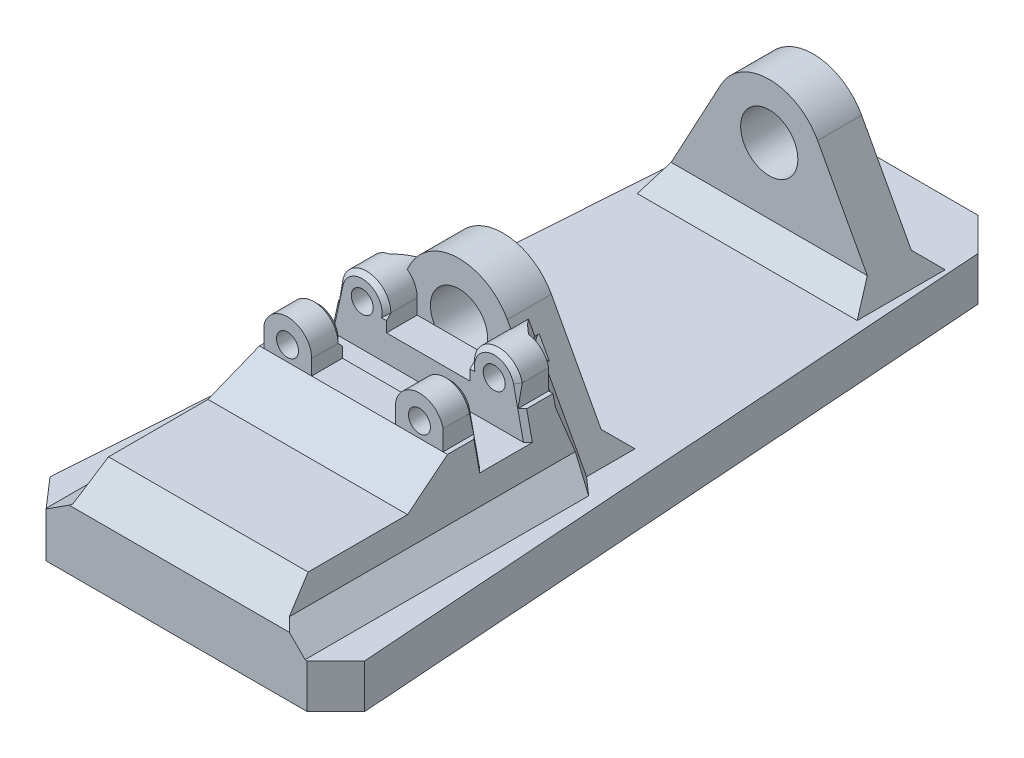
SolidWorks part; units mm, degrees
material "ABS"
ref_plane "Front Plane" through (0, 0, 0) normal (0, 0, 1) x (1, 0, 0)
ref_plane "Top Plane" through (0, 0, 0) normal (0, 1, 0) x (1, 0, 0)
ref_plane "Right Plane" through (0, 0, 0) normal (1, 0, 0) x (0, 0, -1)
sketch "Sketch1" plane through (0, 0, 0) normal (0, 0, 1) x (1, 0, 0)
  line L0 (0, -883.4014) -> (0, -903.4014) construction
  line L1 (-25, -903.4014) -> (25, -903.4014)
  line L2 (-10.9999, -877.464) -> (-25, -903.4014)
  line L3 (25, -903.4014) -> (10.9999, -877.464)
  circle A0 centre (0, -883.4014) radius 6.5
  circle A1 centre (0, -883.4014) radius 12.5
  point P9 (0, -903.4014)
  dimension "D1" = 13
  dimension "D2" = 25
  dimension "D3" = 50
  dimension "D4" = 20
  dimension "D5" = 883.4014
extrude "Boss-Extrude1" add sketch "Sketch1" along normal blind 10
sketch "Sketch2" plane through (0, -903.4014, 0) normal (0, -1, 0) x (1, 0, 0)
  line L0 (25, 10) -> (-25, 10)
  line L1 (25, 10) -> (25, -90)
  line L2 (-25, 10) -> (-25, -90)
  line L3 (25, -90) -> (-25, -90)
  dimension "D1" = 100
extrude "Boss-Extrude2" add sketch "Sketch2" along normal blind 10
ref_plane "Plane1" through (0, 0, -60.5339) normal (0, 0, -1) x (-1, 0, 0)
sketch "Sketch3" plane through (0, 0, -60.5339) normal (0, 0, -1) x (-1, 0, 0)
  line L3 (25, -903.4014) -> (10.9999, -877.464)
  line L4 (-10.9999, -877.464) -> (-25, -903.4014)
  line L5 (-25, -903.4014) -> (25, -903.4014)
  line L6 (25, -903.4014) -> (10.9999, -877.464)
  line L7 (-10.9999, -877.464) -> (-25, -903.4014)
  line L8 (-25, -903.4014) -> (25, -903.4014)
  arc A1 (10.9999, -877.464) -> (-10.9999, -877.464) centre (0, -883.4014) ccw
  arc A2 (10.9999, -877.464) -> (-10.9999, -877.464) centre (0, -883.4014) ccw
  circle A3 centre (0, -883.4014) radius 6.5
  circle A4 centre (0, -883.4014) radius 6.5
  dimension "D1" = 0
  dimension "D2" = 0
extrude "Boss-Extrude3" add sketch "Sketch3" along normal blind 10
chamfer "Chamfer1" distance 5 angle 45 4 edges at (0, -903.4014, 0) (0, -903.4014, -60.5339) (0, -903.4014, -90) (0, -903.4014, -70.5339)
sketch "Sketch4" plane through (0, 0, 10) normal (0, 0, 1) x (1, 0, 0)
  line L4 (-15, -883.4014) -> (15, -883.4014) construction
  line L5 (-9.5, -883.4014) -> (9.5, -883.4014)
  line L7 (25, -913.4014) -> (25, -903.4014) construction
  line L9 (25, -913.4014) -> (-25, -913.4014) construction
  line L10 (25, -903.4014) -> (25, -913.4014)
  line L11 (25, -913.4014) -> (-25, -913.4014)
  line L12 (-25, -913.4014) -> (-25, -903.4014)
  line L13 (-25, -903.4014) -> (-20.3732, -882.2273)
  line L15 (25, -903.4014) -> (20.3732, -882.2273)
  circle A3 centre (0, -883.4014) radius 3 construction
  circle A6 centre (-15, -883.4014) radius 2.5
  circle A7 centre (15, -883.4014) radius 2.5
  arc A8 (-9.5, -883.4014) -> (-20.3732, -882.2273) centre (-15, -883.4014) ccw
  arc A11 (20.3732, -882.2273) -> (9.5, -883.4014) centre (15, -883.4014) ccw
  circle A12 centre (-15, -883.4014) radius 5.5 construction
  circle A13 centre (15, -883.4014) radius 5.5 construction
  point P3 (0, -883.4014)
  point P23 (0, -883.4014)
  dimension "D2" = 5
  dimension "D1" = 30
  dimension "D4" = 25
  dimension "D5" = 10
  dimension "D6" = 30
  dimension "D3" = 3
extrude "Boss-Extrude4" add sketch "Sketch4" along normal blind 7 contours L13 A8 L5 A11 L15 L10 L11 L12 | A6 | A7
sketch "Sketch5" plane through (0, 0, 10) normal (0, 0, 1) x (1, 0, 0)
  circle A8 centre (-15, -883.4014) radius 2.5 construction
  circle A9 centre (15, -883.4014) radius 2.5 construction
  circle A10 centre (-15, -883.4014) radius 2.5
  circle A11 centre (15, -883.4014) radius 2.5
extrude "Cut-Extrude1" cut sketch "Sketch5" against normal blind 5
sketch "Sketch7" plane through (0, 0, 17) normal (0, 0, 1) x (1, 0, 0)
  line L0 (25, -913.4014) -> (25, -903.4014)
  line L1 (25, -913.4014) -> (-25, -913.4014)
  line L2 (25, -903.4014) -> (-25, -903.4014)
  line L3 (-25, -913.4014) -> (-25, -903.4014)
  line L4 (-25, -913.4014) -> (-25, -903.4014) construction
extrude "Boss-Extrude5" add sketch "Sketch7" along normal blind 10
sketch "Sketch8" plane through (0, 0, 27) normal (0, 0, 1) x (1, 0, 0)
  line L4 (-25, -903.4014) -> (25, -903.4014)
  line L5 (25, -903.4014) -> (20.3732, -882.2273)
  line L6 (9.5, -883.4014) -> (-9.5, -883.4014)
  line L7 (-20.3732, -882.2273) -> (-25, -903.4014)
  line L9 (25, -903.4014) -> (20.3732, -882.2273)
  line L10 (9.5, -883.4014) -> (-9.5, -883.4014)
  line L11 (-20.3732, -882.2273) -> (-25, -903.4014)
  line L12 (-25, -913.4014) -> (25, -913.4014)
  line L13 (25, -913.4014) -> (25, -903.4014)
  line L14 (25, -903.4014) -> (-25, -903.4014)
  line L15 (-25, -903.4014) -> (-25, -913.4014)
  line L16 (-25, -913.4014) -> (25, -913.4014)
  line L17 (25, -913.4014) -> (25, -903.4014)
  line L19 (-25, -903.4014) -> (-25, -913.4014)
  circle A1 centre (-15, -883.4014) radius 2.5
  circle A2 centre (-15, -883.4014) radius 2.5
  circle A3 centre (15, -883.4014) radius 2.5
  circle A4 centre (15, -883.4014) radius 2.5
  arc A6 (20.3732, -882.2273) -> (9.5, -883.4014) centre (15, -883.4014) ccw
  arc A7 (-9.5, -883.4014) -> (-20.3732, -882.2273) centre (-15, -883.4014) ccw
  arc A8 (20.3732, -882.2273) -> (9.5, -883.4014) centre (15, -883.4014) ccw
  arc A9 (-9.5, -883.4014) -> (-20.3732, -882.2273) centre (-15, -883.4014) ccw
  dimension "D1" = 0
  dimension "D2" = 0
  dimension "D3" = 0
  dimension "D4" = 0
extrude "Boss-Extrude6" add sketch "Sketch8" along normal blind 7
chamfer "Chamfer3" distance 4 angle 45 2 edges at (-12.5185, -880.2775, 10) (20.2621, -894.6236, 10)
sketch "Sketch11" plane through (0, 0, 27) normal (0, 0, -1) x (-1, 0, 0)
  line L0 (-22.6866, -892.8143) -> (22.6866, -892.8143)
  line L1 (-25, -903.4014) -> (-20.3732, -882.2273) construction
  line L2 (22.6866, -892.8143) -> (25, -903.4014)
  line L3 (25, -903.4014) -> (-25, -903.4014)
  line L4 (-20.3732, -882.2273) -> (-25, -903.4014)
  line L5 (-25, -903.4014) -> (25, -903.4014)
  line L6 (25, -903.4014) -> (20.3732, -882.2273)
  line L7 (9.5, -883.4014) -> (-9.5, -883.4014)
  line L8 (-20.3732, -882.2273) -> (-25, -903.4014) construction
  line L9 (-25, -903.4014) -> (25, -903.4014) construction
  line L10 (25, -903.4014) -> (20.3732, -882.2273) construction
  line L11 (9.5, -883.4014) -> (-9.5, -883.4014) construction
  line L12 (-25, -903.4014) -> (-22.6866, -892.8143)
  arc A2 (20.3732, -882.2273) -> (9.5, -883.4014) centre (15, -883.4014) ccw
  arc A3 (-9.5, -883.4014) -> (-20.3732, -882.2273) centre (-15, -883.4014) ccw
  arc A4 (20.3732, -882.2273) -> (9.5, -883.4014) centre (15, -883.4014) ccw construction
  arc A5 (-9.5, -883.4014) -> (-20.3732, -882.2273) centre (-15, -883.4014) ccw construction
  dimension "D1" = 0
extrude "Boss-Extrude7" add sketch "Sketch11" along normal up to next
chamfer "Chamfer4" distance 1 angle 45 10 edges at (21.5299, -887.5208, 27) (-21.5299, -887.5208, 27) (14.4095, -877.9332, 27) (0, -883.4014, 27) (-14.4095, -877.9332, 27) (21.5299, -887.5208, 17) (-21.5299, -887.5208, 17) (14.4095, -877.9332, 17) (0, -883.4014, 17) (-14.4095, -877.9332, 17)
chamfer "Chamfer5" distance 6 angle 45 2 edges at (10.1067, -880.8903, 10) (-10.1067, -880.8903, 10)
sketch "Sketch12" plane through (0, 0, 34) normal (0, 0, 1) x (1, 0, 0)
  circle A0 centre (0, -883.4014) radius 3 construction
  circle A1 centre (0, -883.4014) radius 3
extrude "Cut-Extrude2" cut sketch "Sketch12" against normal through all
sketch "Sketch13" plane through (0, 0, 34) normal (0, 0, 1) x (1, 0, 0)
  line L0 (22.6866, -892.8143) -> (-22.6866, -892.8143)
  line L1 (25, -903.4014) -> (20.3732, -882.2273) construction
  line L2 (25, -903.4014) -> (20.3732, -882.2273) construction
  line L7 (-3, -883.4014) -> (-9.5, -883.4014)
  line L8 (-20.3732, -882.2273) -> (-25, -903.4014)
  line L9 (-25, -903.4014) -> (-25, -913.4014)
  line L10 (-25, -913.4014) -> (25, -913.4014)
  line L11 (25, -913.4014) -> (25, -903.4014)
  line L12 (25, -903.4014) -> (20.3732, -882.2273)
  line L13 (9.5, -883.4014) -> (3, -883.4014)
  line L15 (-22.6866, -892.8143) -> (-25, -903.4014)
  line L16 (-25, -903.4014) -> (-25, -913.4014)
  line L17 (-25, -913.4014) -> (25, -913.4014)
  line L18 (25, -913.4014) -> (25, -903.4014)
  line L19 (25, -903.4014) -> (22.6866, -892.8143)
  arc A3 (-3, -883.4014) -> (3, -883.4014) centre (0, -883.4014) ccw
  arc A4 (-9.5, -883.4014) -> (-20.3732, -882.2273) centre (-15, -883.4014) ccw
  arc A5 (20.3732, -882.2273) -> (9.5, -883.4014) centre (15, -883.4014) ccw
  dimension "D1" = 0
extrude "Boss-Extrude8" add sketch "Sketch13" along normal blind 40
chamfer "Chamfer6" distance 6 angle 60 1 edges at (0, -892.8143, 34)
chamfer "Chamfer9" distance 7 angle 45 1 edges at (0, -892.8143, 74)
sketch "Sketch14" plane through (0, -913.4014, 0) normal (0, -1, 0) x (1, 0, 0)
  line L0 (25, -90) -> (36.468, 74)
  line L1 (36.468, 74) -> (-36.468, 74)
  line L2 (-36.468, 74) -> (-25, -90)
  line L4 (25, -90) -> (25, 74)
  line L5 (25, 74) -> (-25, 74)
  line L6 (-25, 74) -> (-25, -90)
  line L7 (-25, -90) -> (25, -90)
  line L8 (25, -90) -> (25, 74) construction
  line L9 (25, 74) -> (-25, 74) construction
  line L10 (-25, 74) -> (-25, -90) construction
  line L11 (-25, -90) -> (25, -90)
  dimension "D2" = 4
  dimension "D1" = 0
extrude "Boss-Extrude9" add sketch "Sketch14" against normal blind 10
chamfer "Chamfer10" distance 7 angle 45 4 edges at (-36.468, -908.4014, 74) (-25, -908.4014, -90) (25, -908.4014, -90) (36.468, -908.4014, 74)
chamfer "Chamfer11" distance 4 angle 45 2 edges at (-25, -903.4014, 40) (25, -903.4014, 40)
sketch "Sketch15" plane through (0, 0, 34) normal (0, 0, 1) x (1, 0, 0)
  line L0 (-9.5, -883.4014) -> (-9.5, -886.8143)
  line L1 (-21.3755, -886.8143) -> (21.3755, -886.8143) construction
  line L2 (-9.5, -886.8143) -> (9.5, -886.8143)
  line L3 (9.5, -886.8143) -> (9.5, -883.4014)
  line L5 (11.7929, -878.9332) -> (10.9999, -877.464) construction
  line L6 (-10.9999, -877.464) -> (-11.7929, -878.9332) construction
  line L7 (11.7929, -878.9332) -> (10.9999, -877.464)
  line L8 (-10.9999, -877.464) -> (-11.7929, -878.9332)
  arc A0 (-9.5, -883.4014) -> (-20.3732, -882.2273) centre (-15, -883.4014) ccw construction
  arc A1 (20.3732, -882.2273) -> (9.5, -883.4014) centre (15, -883.4014) ccw construction
  arc A2 (11.7929, -878.9332) -> (9.5, -883.4014) centre (15, -883.4014) ccw
  arc A3 (-9.5, -883.4014) -> (-11.7929, -878.9332) centre (-15, -883.4014) ccw
  arc A4 (10.9999, -877.464) -> (-10.9999, -877.464) centre (0, -883.4014) ccw construction
  arc A5 (10.9999, -877.464) -> (-10.9999, -877.464) centre (0, -883.4014) ccw
extrude "Cut-Extrude3" cut sketch "Sketch15" against normal up to surface (24 mm away)
sketch "Sketch16" plane through (0, 0, 34) normal (0, 0, 1) x (1, 0, 0)
  line L0 (20.3732, -882.2273) -> (20.3732, -886.8143)
  line L1 (9.5, -886.8143) -> (21.3755, -886.8143) construction
  line L2 (20.3732, -886.8143) -> (21.3755, -886.8143)
  line L3 (21.3755, -886.8143) -> (20.3732, -882.2273) construction
  line L4 (21.3755, -886.8143) -> (20.3732, -882.2273)
  line L5 (-20.3732, -882.2273) -> (-20.3732, -886.8143)
  line L6 (-21.3755, -886.8143) -> (-9.5, -886.8143) construction
  line L7 (-20.3732, -886.8143) -> (-21.3755, -886.8143)
  line L8 (-21.3755, -886.8143) -> (-20.3732, -882.2273)
extrude "Cut-Extrude4" cut sketch "Sketch16" against normal up to surface (24 mm away)
